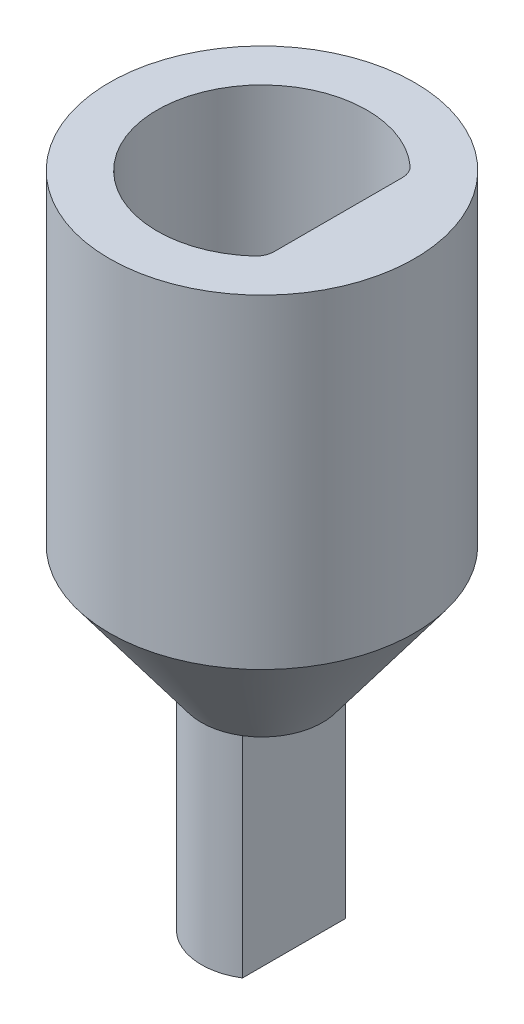
SolidWorks part; units mm, degrees
ref_plane "Front Plane" through (0, 0, 0) normal (0, 0, 1) x (1, 0, 0)
ref_plane "Top Plane" through (0, 0, 0) normal (0, 1, 0) x (1, 0, 0)
ref_plane "Right Plane" through (0, 0, 0) normal (1, 0, 0) x (0, 0, -1)
sketch "Sketch1" plane through (0, 0, 0) normal (0, 1, 0) x (1, 0, 0)
  line L1 (4, 0.0342) -> (4, 3.7749)
  line L2 (4, 0.0342) -> (4, -3.7749)
  arc A0 (4, 3.7749) -> (4, -3.7749) centre (0, 0) ccw
  circle A1 centre (0, 0) radius 8
  dimension "D1" = 11
  dimension "D2" = 16
extrude "Boss-Extrude1" add sketch "Sketch1" along normal blind 12
sketch "Sketch2" plane through (0, 0, 0) normal (0, 0, 1) x (1, 0, 0)
  line L0 (8, 0) -> (8, -5)
  line L1 (3.175, -22.4737) -> (0, -22.4737)
  line L2 (8, -5) -> (3.175, -11.4737)
  line L3 (3.175, -11.4737) -> (3.175, -22.4737)
  line L4 (0, -22.4737) -> (0, 0)
  line L5 (0, -22.4737) -> (0, -30.3228) construction
  line L6 (8, 0) -> (0, 0)
  dimension "D1" = 5
  dimension "D3" = 11
revolve "Revolve1" add sketch "Sketch2" angle 360 about L5
sketch "Sketch3" plane through (0, 0, 0) normal (0, 0, 1) x (1, 0, 0)
  line L0 (3.175, -22.4737) -> (1.675, -22.4737)
  line L1 (-3.175, -22.4737) -> (3.175, -22.4737) construction
  line L2 (1.675, -22.4737) -> (1.675, -11.4737)
  line L3 (3.175, -11.4737) -> (-3.175, -11.4737) construction
  line L4 (1.675, -11.4737) -> (3.175, -11.4737)
  line L5 (3.175, -11.4737) -> (3.175, -22.4737)
  dimension "D1" = 1.5
extrude "Cut-Extrude1" cut sketch "Sketch3" against normal blind 12 and the other way blind 12
fillet "Fillet2" radius 1 1 edges at (4, 6, -3.7749)
fillet "Fillet3" radius 1 1 edges at (4, 6, 3.7749)
